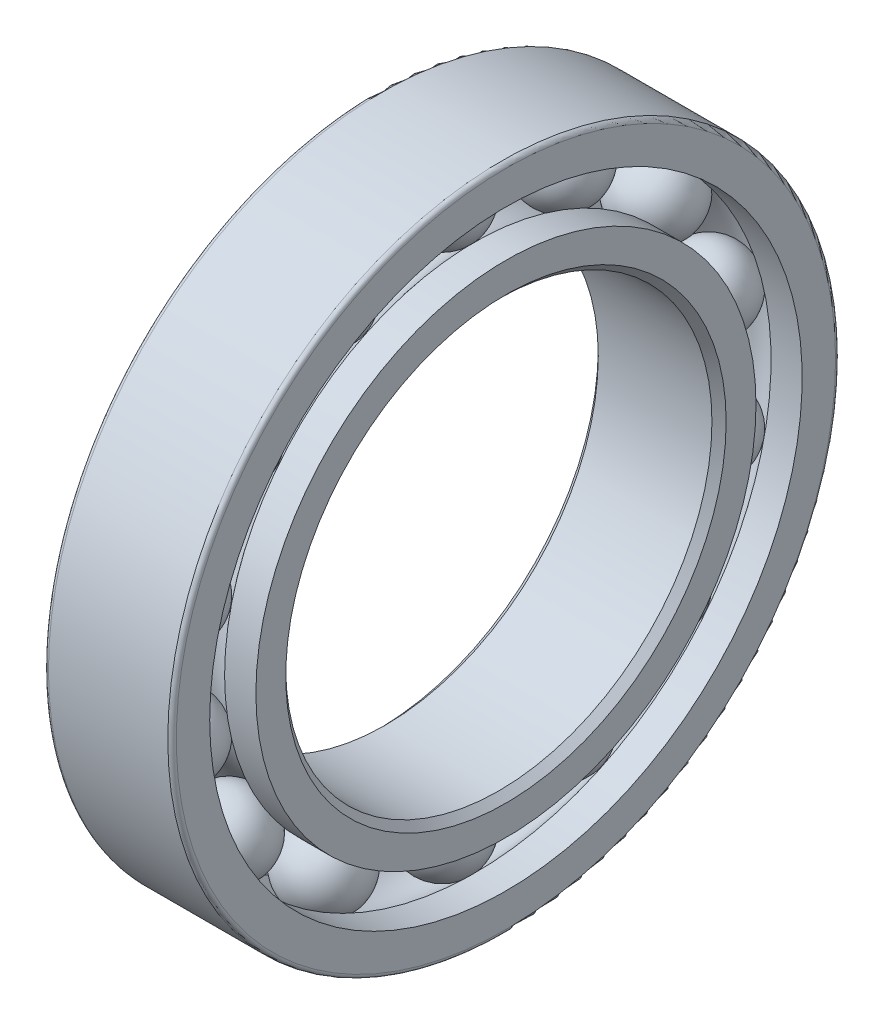
SolidWorks part; units mm, degrees
ref_plane "Front Plane" through (0, 0, 0) normal (0, 0, 1) x (1, 0, 0)
ref_plane "Top Plane" through (0, 0, 0) normal (0, 1, 0) x (1, 0, 0)
ref_plane "Right Plane" through (0, 0, 0) normal (1, 0, 0) x (0, 0, -1)
sketch "Sketch1" plane through (0, 0, 0) normal (0, 0, 1) x (1, 0, 0)
  line L0 (-39.0341, 0) -> (0, 0) construction
  line L1 (0, 0) -> (0, 22.175) construction
  line L3 (4.5, 23.5) -> (-4.5, 23.5)
  line L4 (4.5, 23.5) -> (4.5, 20.85)
  line L5 (4.5, 20.85) -> (-4.5, 20.85)
  line L6 (-4.5, 23.5) -> (-4.5, 20.85)
  line L7 (4.5, 23.5) -> (-4.5, 20.85) construction
  line L8 (4.5, 20.85) -> (-4.5, 23.5) construction
  line L9 (4.5, 17.6) -> (-4.5, 17.6)
  line L10 (4.5, 17.6) -> (4.5, 15)
  line L11 (4.5, 15) -> (-4.5, 15)
  line L12 (-4.5, 17.6) -> (-4.5, 15)
  line L13 (4.5, 17.6) -> (-4.5, 15) construction
  line L14 (4.5, 15) -> (-4.5, 17.6) construction
  circle A0 centre (0, 19.2353) radius 2.82
  point P9 (0, 16.3)
  dimension "D1" = 15
  dimension "D2" = 23.5
  dimension "D3" = 9
  dimension "D4" = 17.6
  dimension "D5" = 20.85
revolve "Revolve1" add sketch "Sketch1" angle 360 about L0 region at (0, 22.3383, 0) region at (0, 16.141, 0)
sketch "Sketch2" plane through (0, 0, 0) normal (0, 0, 1) x (1, 0, 0)
  line L0 (-2.8, 19.24) -> (2.8, 19.24)
  circle A0 centre (0, 19.24) radius 2.8
  dimension "D1" = 19.24
  dimension "D2" = 5.6
revolve "Revolve2" add sketch "Sketch2" angle 360 about L0 region at (0, 20.4284, 0)
ref_axis "Axis1" through (4.5, 0, 0) along (-1, 0, 0)
pattern_circular "CirPattern1" count 14 over 360 about axis through (4.5, 0, 0) along (-1, 0, 0) of bodies 103
fillet "Fillet1" radius 0.3 2 edges at (4.5, 0, 23.5) (-4.5, 0, 23.5)
chamfer "Chamfer1" distance 0.5 angle 45 2 edges at (4.5, 0, 15) (-4.5, 0, 15)
